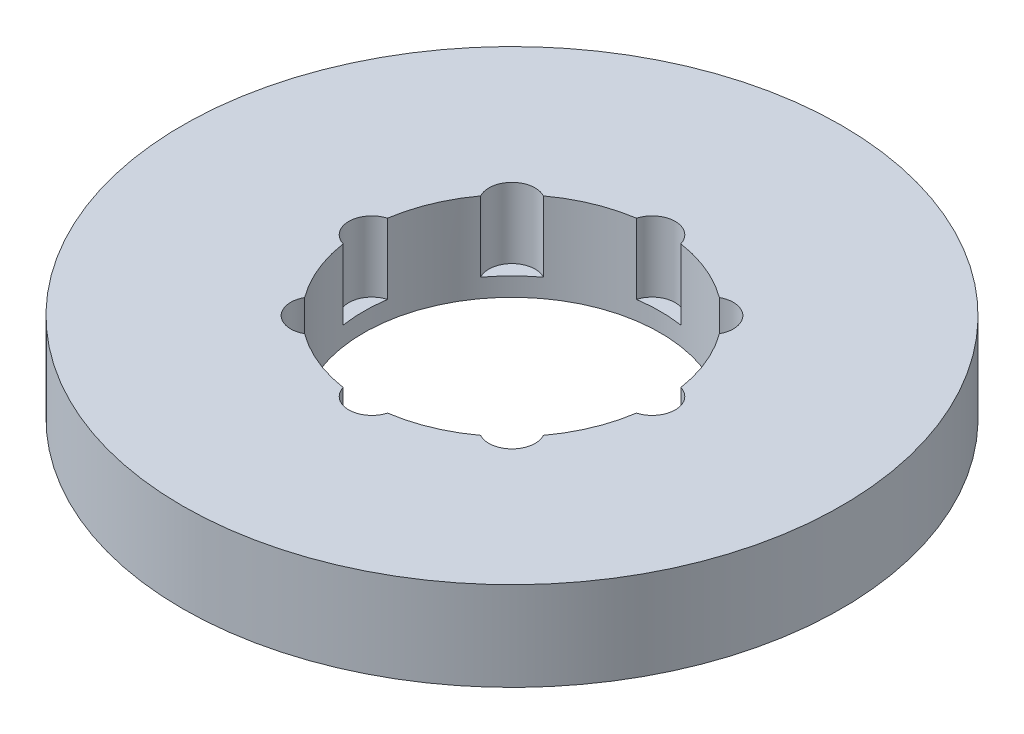
SolidWorks part; units mm, degrees
ref_plane "Front Plane" through (0, 0, 0) normal (0, 0, 1) x (1, 0, 0)
ref_plane "Top Plane" through (0, 0, 0) normal (0, 1, 0) x (1, 0, 0)
ref_plane "Right Plane" through (0, 0, 0) normal (1, 0, 0) x (0, 0, -1)
sketch "Sketch1" plane through (0, 0, 0) normal (0, 1, 0) x (1, 0, 0)
  circle A0 centre (0, 0) radius 100
  dimension "FLANGE_OD" = 200
extrude "Boss-Extrude1" add sketch "Sketch1" along normal blind 27
sketch "Sketch2" plane through (0, 0, 0) normal (0, 1, 0) x (1, 0, 0)
  circle A0 centre (0, 0) radius 45
  dimension "BORE_D" = 90
extrude "Cut-Extrude1" cut sketch "Sketch2" along normal through all
sketch "Sketch3" plane through (0, 27, 0) normal (0, 1, 0) x (1, 0, 0)
  circle A0 centre (0, 0) radius 42.5242 construction
  circle A1 centre (-42.5242, 0) radius 7.0118
  dimension "BOLT_D" = 14.0236
  dimension "BOLT_PCD" = 85.0484
extrude "Cut-Extrude2" cut sketch "Sketch3" against normal blind 21.3523
pattern_circular "CirPattern1" count 8 over 360 about axis through (0, 0, 0) along (0, 1, 0) of "Cut-Extrude2"
